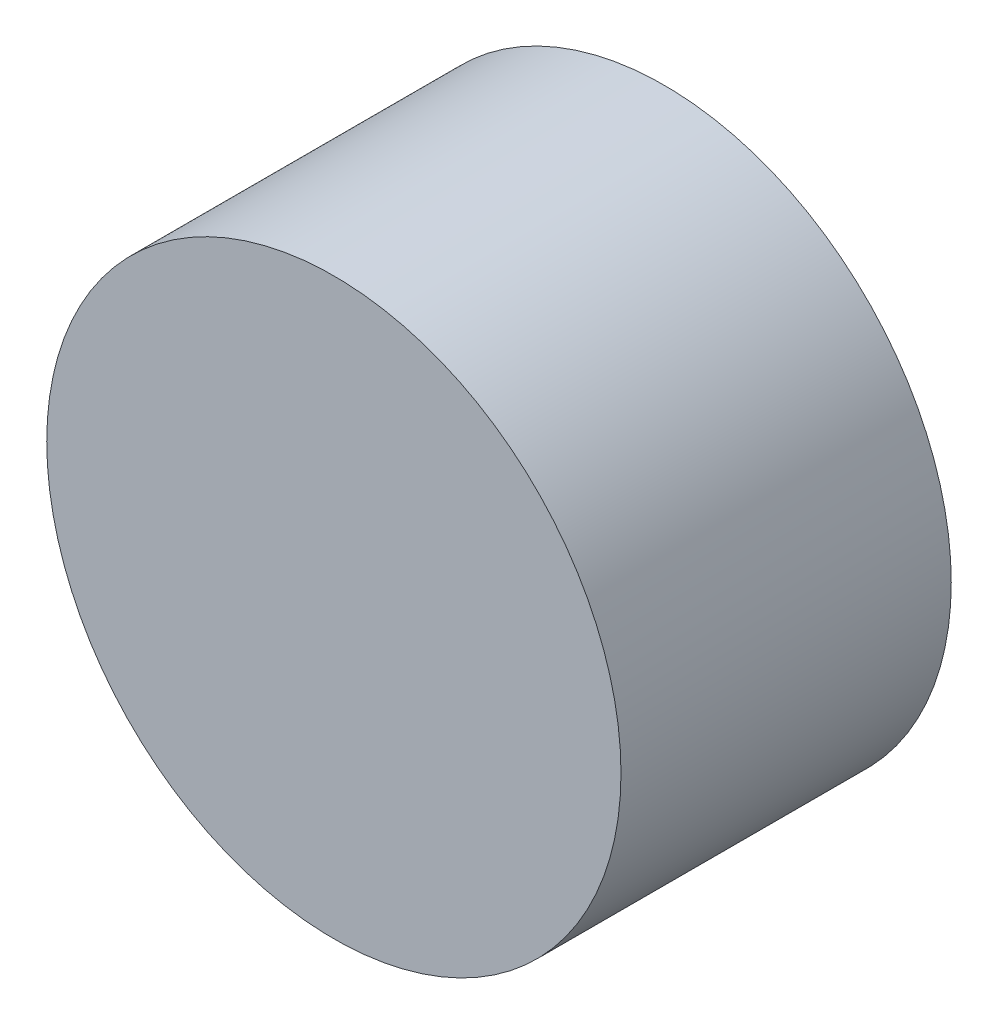
SolidWorks part; units mm, degrees
ref_plane "xy_plane" through (0, 0, 0) normal (0, 0, 1) x (1, 0, 0)
ref_plane "zx_plane" through (0, 0, 0) normal (0, 1, 0) x (1, 0, 0)
ref_plane "yz_plane" through (0, 0, 0) normal (1, 0, 0) x (0, 0, -1)
ref_plane "xMid_plane" through (0, 0, 0) normal (1, 0, 0) x (0, 0, -1)
ref_plane "xMin_plane" through (-0.6173, 0, 0) normal (1, 0, 0) x (0, 0, -1)
ref_plane "xMax_plane" through (0.6173, 0, 0) normal (1, 0, 0) x (0, 0, -1)
ref_plane "yMid_plane" through (0, 0, 0) normal (0, 1, 0) x (1, 0, 0)
ref_plane "yMin_plane" through (0, -0.6173, 0) normal (0, 1, 0) x (1, 0, 0)
ref_plane "yMax_plane" through (0, 0.6173, 0) normal (0, 1, 0) x (1, 0, 0)
ref_plane "zMid_plane" through (0, 0, 0) normal (0, 0, 1) x (1, 0, 0)
ref_plane "zMin_plane" through (0, 0, -0.6173) normal (0, 0, 1) x (1, 0, 0)
ref_plane "zMax_plane" through (0, 0, 0.6173) normal (0, 0, 1) x (1, 0, 0)
ref_axis "x_axis" through (-80.9, 0, 0) along (1, 0, 0)
ref_axis "y_axis" through (0, -50, 0) along (0, 1, 0)
ref_axis "z_axis" through (0, 0, -80.9) along (0, 0, 1)
sketch "Sketch1" plane through (0, 0, 0) normal (0, 0, 1) x (1, 0, 0)
  circle A0 centre (0, 0) radius 8.6936
extrude "Boss-Extrude1" add sketch "Sketch1" along normal blind 10
equation "\"D1@xMin_plane\"=\"externalParameters.this.extentX\"/2"
equation "\"D1@xMax_plane\"=\"externalParameters.this.extentX\"/2"
equation "\"D1@yMin_plane\"=\"externalParameters.this.extentY\"/2"
equation "\"D1@yMax_plane\"=\"externalParameters.this.extentY\"/2"
equation "\"D1@zMin_plane\"=\"externalParameters.this.extentZ\"/2"
equation "\"D1@zMax_plane\"=\"externalParameters.this.extentZ\"/2"
